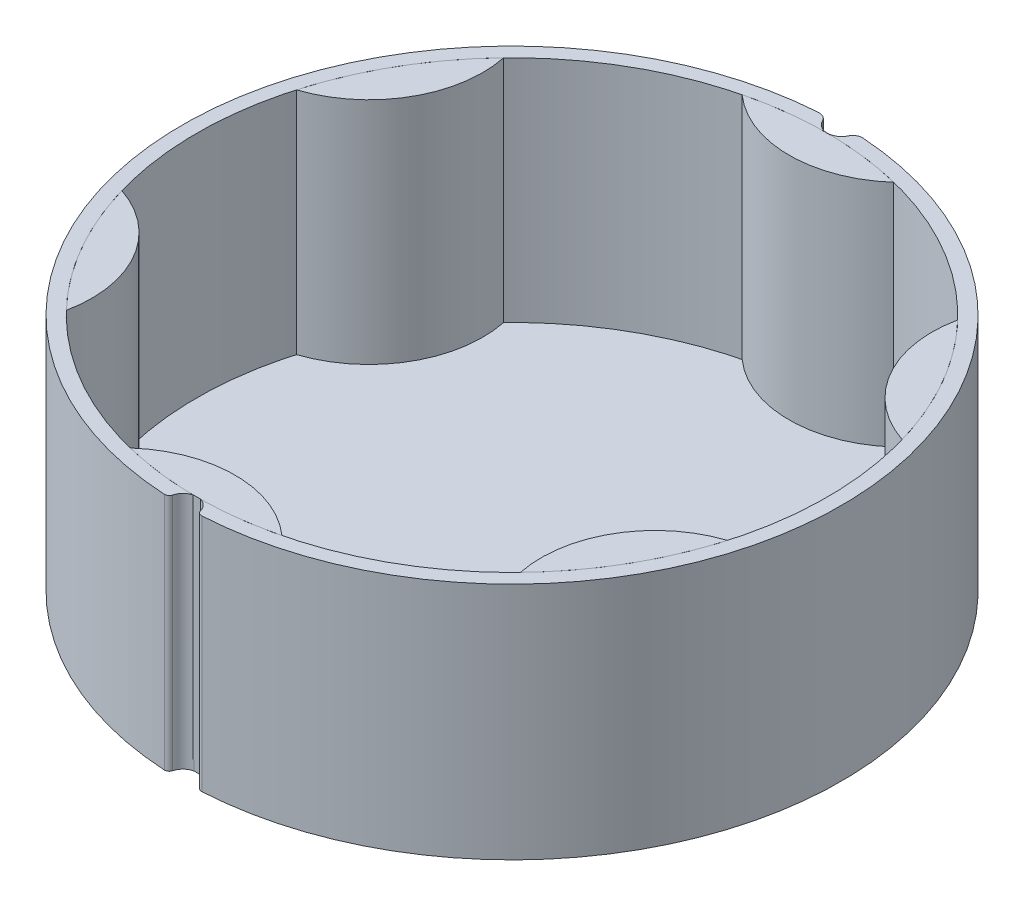
SolidWorks part; units mm, degrees
other "Markup1"
sketch "Sketch4" plane through (-34.5, 25, 34.4428) normal (-0.055, 0.9636, 0.2616) x (0.9976, 0.0639, -0.0258)
other "Markup3"
sketch "Sketch6"
other "DetailItem2"
other "Markup5"
sketch "Sketch8" plane through (34.5, 25, 34.4428) normal (0.0041, 0.9851, 0.1719) x (0.981, -0.0374, 0.1906)
other "Markup6"
sketch "Sketch9" plane through (34.5, 25, 34.4428) normal (0.0041, 0.9851, 0.1719) x (0.981, -0.0374, 0.1906)
other "Markup7"
sketch "Sketch10" plane through (-34.5, 25, 34.4428) normal (-0.125, 0.9874, 0.0969) x (0.5933, -0.0039, 0.805)
ref_plane "Front Plane" through (0, 0, 0) normal (0, 0, 1) x (1, 0, 0)
ref_plane "Top Plane" through (0, 0, 0) normal (0, 1, 0) x (1, 0, 0)
ref_plane "Right Plane" through (0, 0, 0) normal (1, 0, 0) x (0, 0, -1)
sketch "Sketch1" plane through (0, 0, 0) normal (0, 1, 0) x (1, 0, 0)
  line L3 (0, 0.002) -> (0, 3.7877) construction
  line L4 (0, 3.7877) -> (2.417, 3.7877)
  line L5 (0, 3.7877) -> (-2.417, 3.7877)
  arc A0 (1.9642, -34.442) -> (34.1982, 4.5552) centre (0, 0.002) ccw
  arc A2 (-2.417, 3.7877) -> (2.417, 3.7877) centre (0, 0.002) ccw
  circle A3 centre (0, 0.002) radius 34.5 construction
  arc A7 (-1.3541, 33.8562) -> (1.3541, 33.8562) centre (0, 34.5015) ccw
  arc A8 (34.1982, 4.5552) -> (2.3241, 34.4236) centre (0, 0.002) ccw
  arc A9 (-2.3241, 34.4236) -> (-34.1982, 4.5552) centre (0, 0.002) ccw
  arc A10 (-34.1982, 4.5552) -> (-1.9642, -34.442) centre (0, 0.002) ccw
  arc A11 (1.3541, 33.8562) -> (2.3241, 34.4236) centre (2.2568, 33.4259) cw
  arc A12 (-1.3541, 33.8562) -> (-2.3241, 34.4236) centre (-2.2568, 33.4259) ccw
  arc A13 (1.4518, -34.0686) -> (-1.4518, -34.0686) centre (0, -34.4457) ccw
  arc A14 (1.4518, -34.0686) -> (1.9642, -34.442) centre (1.9358, -33.9428) ccw
  arc A15 (-1.4518, -34.0686) -> (-1.9642, -34.442) centre (-1.9358, -33.9428) cw
  point P15 (1.4997, 34.4694)
  dimension "D2" = 4.834
  dimension "D3" = 4.4915
  dimension "D4" = 34.5
  dimension "D5" = 1
  dimension "D6" = 1.5
  dimension "D7" = 0.5
  dimension "D11" = 1.4997
sketch "Sketch2" plane through (0, 0, 0) normal (0, 1, 0) x (1, 0, 0)
  line L0 (0, 33) -> (0, 29) construction
  line L1 (-7.941, 32.0303) -> (0, 33) construction
  line L2 (0, 33) -> (7.941, 32.0303) construction
  circle A16 centre (0, 0) radius 33
  arc A17 (-7.941, 32.0303) -> (7.941, 32.0303) centre (0, 40.92) ccw
  dimension "D1" = 66
  dimension "D2" = 8
  dimension "D3" = 4
extrude "Boss-Extrude1" add sketch "Sketch1" along normal blind 25 contours A10 A0 A8 A7 A9 A2 L5 L4 | L5 A2 L4 region at (0, 0, 0.1522) region at (2.2155, 0, 33.5591)
extrude "Cut-Extrude2" cut sketch "Sketch2" along normal up to next from offset 1 contours A17 A16 | A16 region at (0, 0, 0.3998)
extrude "Boss-Extrude2" add sketch "Sketch2<2>" along normal up to surface (25 mm away) separate body contours A16 A17 region at (0, 0, -31.188) up to face at (0, 25, 0.1251)
sketch "Sketch2<2>" plane through (0, 0, 0) normal (0, 1, 0) x (1, 0, 0) same geometry as "Sketch2"
pattern_circular "CirPattern2" count 6 over 360 about axis through (0, 25, 0) along (0, 1, 0) of bodies 106
sketch "Sketch3" plane through (0, 25, 0) normal (0, 1, 0) x (1, 0, 0)
  line L0 (23.7685, -22.8923) -> (16.5, -28.5788) construction
  line L1 (16.5, -28.5788) -> (7.941, -32.0303) construction
  line L2 (-7.941, 32.0303) -> (-16.5, 28.5788) construction
  line L3 (-16.5, 28.5788) -> (-23.7685, 22.8923) construction
  line L4 (31.7096, 9.138) -> (33, 0) construction
  line L5 (33, 0) -> (31.7096, -9.138) construction
  line L6 (-31.7096, 9.138) -> (-33, 0) construction
  line L7 (-33, 0) -> (-31.7096, -9.138) construction
  arc A0 (0.3915, -32.9977) -> (-0.3915, -32.9977) centre (0, 0) ccw construction
